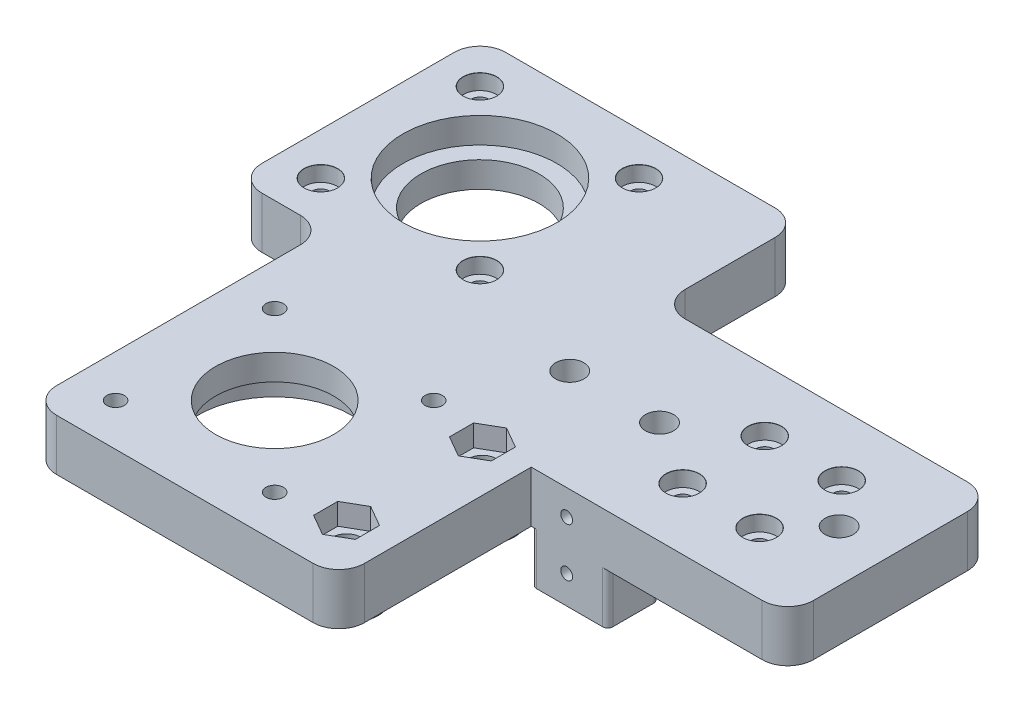
SolidWorks part; units mm, degrees
ref_plane "Front Plane" through (0, 0, 0) normal (0, 0, 1) x (1, 0, 0)
ref_plane "Top Plane" through (0, 0, 0) normal (0, 1, 0) x (1, 0, 0)
ref_plane "Right Plane" through (0, 0, 0) normal (1, 0, 0) x (0, 0, -1)
sketch "Sketch1" plane through (0, 0, 0) normal (0, 1, 0) x (1, 0, 0)
  line L0 (0, 0) -> (110, 0) construction
  line L1 (110, 0) -> (110, 20) construction
  line L2 (110, 20) -> (0, 20) construction
  line L3 (0, 20) -> (0, 0) construction
  line L4 (110, 30) -> (110, -10) construction
  line L5 (110, 30) -> (80, 30) construction
  line L6 (80, 30) -> (80, -10) construction
  line L7 (80, -10) -> (110, -10) construction
  line L8 (0, 67.5) -> (0, -47.5)
  line L16 (0, 67.5) -> (60, 67.5)
  line L18 (0, -47.5) -> (60, -47.5)
  line L19 (60, 67.5) -> (60, 30)
  line L22 (110, -10) -> (60, -10)
  line L23 (60, -10) -> (60, -47.5)
  line L24 (60, 30) -> (110, 30)
  line L25 (110, 30) -> (110, -10)
  point P8 (110, 10)
  point P13 (0, 10)
  dimension "D1" = 20
  dimension "D2" = 37.5
  dimension "D3" = 30
  dimension "D4" = 40
  dimension "D5" = 110
  dimension "D6" = 20
extrude "Boss-Extrude1" add sketch "Sketch1" along normal blind 10
fillet "Fillet1" radius 5 7 edges at (60, 5, -30) (110, 5, -30) (110, 5, 10) (0, 5, 47.5) (0, 5, -67.5) (60, 5, -67.5) (60, 5, 47.5)
sketch "Sketch3" plane through (0, 10, 0) normal (0, 1, 0) x (1, 0, 0)
  line L0 (5, -47.5) -> (55, -47.5) construction
  line L1 (0, 62.5) -> (0, -42.5) construction
  circle A0 centre (23.75, -23.75) radius 11.5
  dimension "D3" = 23
  dimension "D1" = 23.75
  dimension "D2" = 23.75
extrude "Cut-Extrude1" cut sketch "Sketch3" against normal blind 10
sketch "Sketch4" plane through (0, 0, 0) normal (0, -1, 0) x (1, 0, 0)
  line L1 (39.25, 39.25) -> (8.25, 39.25)
  line L2 (39.25, 39.25) -> (39.25, 8.25)
  line L3 (39.25, 8.25) -> (8.25, 8.25)
  line L4 (8.25, 39.25) -> (8.25, 8.25)
  line L5 (39.25, 39.25) -> (8.25, 8.25) construction
  line L6 (39.25, 8.25) -> (8.25, 39.25) construction
  point P0 (23.75, 23.75)
  dimension "D1" = 31
hole_wizard "CBORE for M3 SHCS1" positions "Sketch5" profile "Sketch6" counterbore size "M3" standard "ANSI Metric" end condition through all
sketch "Sketch5" plane through (0, 0, 0) normal (0, -1, 0) x (-1, 0, 0)
  point P0 (-39.25, -8.25)
  point P3 (-8.25, -39.25)
  point P6 (-8.25, -8.25)
  point P9 (-39.25, -39.25)
sketch "Sketch6" plane through (39.25, 0, 8.25) normal (1, 0, 0) x (0, 0, -1)
  line L0 (0, 0) -> (0, 10)
  line L1 (0, 10) -> (1.7, 10)
  line L3 (1.7, 10) -> (1.7, 3)
  line L4 (3.25, 3) -> (1.7, 3)
  line L5 (3.25, 3) -> (3.25, 0.025)
  line L6 (3.25, 0.025) -> (3.275, 0)
  line L7 (3.275, 0) -> (0, 0)
  line L8 (-3.25, 0.025) -> (-3.275, 0) construction
  line L11 (0, -6.35) -> (0, 107.95) construction
  dimension "Thru Hole Dia." = 3.4
  dimension "Thru Hole Depth" = 10
  dimension "C'Bore Dia." = 6.5
  dimension "C'Bore Depth" = 3
  dimension "Near C'Sink Dia." = 6.55
  dimension "Near C'Sink Angle" = 90
sketch "Sketch7" plane through (0, 10, 0) normal (0, 1, 0) x (1, 0, 0)
  line L1 (92.5, 18) -> (77.5, 18)
  line L2 (92.5, 18) -> (92.5, 2)
  line L3 (92.5, 2) -> (77.5, 2)
  line L4 (77.5, 18) -> (77.5, 2)
  line L5 (92.5, 18) -> (77.5, 2) construction
  line L6 (92.5, 2) -> (77.5, 18) construction
  line L7 (110, 10) -> (0, 10)
  line L8 (0, 67.5) -> (0, -47.5) construction
  line L10 (110, 30) -> (110, -10) construction
  point P0 (85, 10)
  dimension "D1" = 15
  dimension "D2" = 16
  dimension "D3" = 25
hole_wizard "CBORE for M3 SHCS2" positions "Sketch8" profile "Sketch9" counterbore size "M3" standard "ANSI Metric" end condition through all
sketch "Sketch8" plane through (0, 10, 0) normal (0, 1, 0) x (1, 0, 0)
  point P0 (77.5, 18)
  point P3 (92.5, 18)
  point P6 (92.5, 2)
  point P9 (77.5, 2)
sketch "Sketch9" plane through (77.5, 10, -18) normal (1, 0, 0) x (0, 0, 1)
  line L0 (0, 0) -> (0, 10)
  line L1 (0, 10) -> (1.7, 10)
  line L3 (1.7, 10) -> (1.7, 3)
  line L4 (3.25, 3) -> (1.7, 3)
  line L5 (3.25, 3) -> (3.25, 0.025)
  line L6 (3.25, 0.025) -> (3.275, 0)
  line L7 (3.275, 0) -> (0, 0)
  line L8 (-3.25, 0.025) -> (-3.275, 0) construction
  line L11 (0, -6.35) -> (0, 107.95) construction
  dimension "Thru Hole Dia." = 3.4
  dimension "Thru Hole Depth" = 10
  dimension "C'Bore Dia." = 6.5
  dimension "C'Bore Depth" = 3
  dimension "Near C'Sink Dia." = 6.55
  dimension "Near C'Sink Angle" = 90
sketch "Sketch10" plane through (0, 0, 0) normal (0, -1, 0) x (1, 0, 0)
  line L0 (110, -10) -> (0, -10) construction
  line L1 (110, 5) -> (110, -25) construction
  line L2 (0, -62.5) -> (0, 42.5) construction
  point P6 (100, -10)
  point P7 (30, -10)
  point P8 (47.5, -10)
  point P9 (65, -10)
  dimension "D1" = 30
  dimension "D2" = 17.5
  dimension "D3" = 17.5
  dimension "D4" = 10
hole_wizard "CBORE for M5 SHCS1" positions "Sketch13" profile "Sketch12" counterbore size "M5" standard "ANSI Metric" end condition through all
sketch "Sketch13" plane through (0, 0, 0) normal (0, -1, 0) x (-1, 0, 0)
  point P0 (-100, 10)
  point P3 (-65, 10)
  point P6 (-47.5, 10)
  point P13 (0, 0)
sketch "Sketch12" plane through (100, 0, -10) normal (1, 0, 0) x (0, 0, -1)
  line L0 (0, 0) -> (0, 10)
  line L1 (0, 10) -> (2.75, 10)
  line L3 (2.75, 10) -> (2.75, 5)
  line L4 (5, 5) -> (2.75, 5)
  line L5 (5, 5) -> (5, 0.025)
  line L6 (5, 0.025) -> (5.025, 0)
  line L7 (5.025, 0) -> (0, 0)
  line L8 (-5, 0.025) -> (-5.025, 0) construction
  line L11 (0, -6.35) -> (0, 107.95) construction
  dimension "Thru Hole Dia." = 5.5
  dimension "Thru Hole Depth" = 10
  dimension "C'Bore Dia." = 10
  dimension "C'Bore Depth" = 5
  dimension "Near C'Sink Dia." = 10.05
  dimension "Near C'Sink Angle" = 90
sketch "Sketch14" plane through (0, 10, 0) normal (0, 1, 0) x (1, 0, 0)
  line L0 (0, 10) -> (-17.5, 10)
  line L1 (0, 62.5) -> (0, -42.5) construction
  line L2 (-17.5, 10) -> (-17.5, 67.5)
  line L3 (-17.5, 67.5) -> (5, 67.5)
  line L4 (0, 62.5) -> (0, 10)
  arc A0 (5, 67.5) -> (0, 62.5) centre (5, 62.5) ccw construction
  arc A1 (5, 67.5) -> (0, 62.5) centre (5, 62.5) ccw
  dimension "D1" = 17.5
extrude "Boss-Extrude2" add sketch "Sketch14" against normal blind 10
sketch "Sketch15" plane through (0, 10, 0) normal (0, 1, 0) x (1, 0, 0)
  line L0 (-17.5, 67.5) -> (55, 67.5)
  line L1 (-17.5, 67.5) -> (-17.5, 57.5)
  line L2 (-17.5, 67.5) -> (-17.5, 10) construction
  line L3 (-17.5, 57.5) -> (60, 57.5)
  line L5 (60, 35) -> (60, 62.5) construction
  line L6 (60, 57.5) -> (60, 62.5)
  arc A2 (60, 62.5) -> (55, 67.5) centre (55, 62.5) ccw construction
  arc A3 (60, 62.5) -> (55, 67.5) centre (55, 62.5) ccw
  dimension "D1" = 10
extrude "Cut-Extrude2" cut sketch "Sketch15" against normal blind 10
fillet "Fillet2" radius 5 4 edges at (0, 5, -10) (60, 5, -57.5) (-17.5, 5, -57.5) (-17.5, 5, -10)
sketch "Sketch16" plane through (0, 10, 0) normal (0, 1, 0) x (1, 0, 0)
  line L0 (-12.5, 57.5) -> (55, 57.5) construction
  line L1 (-17.5, 52.5) -> (-17.5, 15) construction
  circle A0 centre (6.25, 33.75) radius 11.5
  dimension "D1" = 23
  dimension "D2" = 23.75
  dimension "D3" = 23.75
extrude "Cut-Extrude3" cut sketch "Sketch16" against normal through all
sketch "Sketch17" plane through (0, 10, 0) normal (0, 1, 0) x (1, 0, 0)
  line L1 (21.75, 49.25) -> (-9.25, 49.25)
  line L2 (21.75, 49.25) -> (21.75, 18.25)
  line L3 (21.75, 18.25) -> (-9.25, 18.25)
  line L4 (-9.25, 49.25) -> (-9.25, 18.25)
  line L5 (21.75, 49.25) -> (-9.25, 18.25) construction
  line L6 (21.75, 18.25) -> (-9.25, 49.25) construction
  point P0 (6.25, 33.75)
  dimension "D1" = 31
hole_wizard "CBORE for M3 SHCS3" positions "Sketch18" profile "Sketch19" counterbore size "M3" standard "ANSI Metric" end condition through all
sketch "Sketch18" plane through (0, 10, 0) normal (0, 1, 0) x (1, 0, 0)
  point P0 (-9.25, 49.25)
  point P3 (21.75, 49.25)
  point P6 (21.75, 18.25)
  point P9 (-9.25, 18.25)
sketch "Sketch19" plane through (-9.25, 10, -49.25) normal (1, 0, 0) x (0, 0, 1)
  line L0 (0, 0) -> (0, 10)
  line L1 (0, 10) -> (1.7, 10)
  line L3 (1.7, 10) -> (1.7, 3)
  line L4 (3.25, 3) -> (1.7, 3)
  line L5 (3.25, 3) -> (3.25, 0.025)
  line L6 (3.25, 0.025) -> (3.275, 0)
  line L7 (3.275, 0) -> (0, 0)
  line L8 (-3.25, 0.025) -> (-3.275, 0) construction
  line L11 (0, -6.35) -> (0, 107.95) construction
  dimension "Thru Hole Dia." = 3.4
  dimension "Thru Hole Depth" = 10
  dimension "C'Bore Dia." = 6.5
  dimension "C'Bore Depth" = 3
  dimension "Near C'Sink Dia." = 6.55
  dimension "Near C'Sink Angle" = 90
sketch "Sketch20" plane through (0, 10, 0) normal (0, 1, 0) x (1, 0, 0)
  line L0 (23.75, -23.75) -> (60, -23.75) construction
  line L1 (60, -42.5) -> (60, -10) construction
  line L2 (51, -10.51) -> (51, -36.99) construction
  line L4 (55.0703, -8.16) -> (51, -5.81)
  line L5 (51, -5.81) -> (46.9297, -8.16)
  line L6 (46.9297, -8.16) -> (46.9297, -12.86)
  line L7 (46.9297, -12.86) -> (51, -15.21)
  line L8 (51, -15.21) -> (55.0703, -12.86)
  line L9 (55.0703, -12.86) -> (55.0703, -8.16)
  line L10 (51, -32.29) -> (46.9297, -34.64)
  line L11 (46.9297, -34.64) -> (46.9297, -39.34)
  line L12 (46.9297, -39.34) -> (51, -41.69)
  line L13 (51, -41.69) -> (55.0703, -39.34)
  line L14 (55.0703, -39.34) -> (55.0703, -34.64)
  line L15 (55.0703, -34.64) -> (51, -32.29)
  line L18 (0, 5) -> (0, -42.5) construction
  circle A0 centre (51, -10.51) radius 4.0703 construction
  circle A1 centre (51, -36.99) radius 4.0703 construction
  point P8 (51, -23.75)
  point P25 (51, -36.99)
  point P26 (51, -10.51)
  dimension "D1" = 26.48
  dimension "D2" = 9
  dimension "D3" = 4.7
extrude "Cut-Extrude4" cut sketch "Sketch20" against normal blind 4.2
hole_wizard "M5 Clearance Hole1" positions "Sketch22" profile "Sketch23" hole size "M5" standard "ANSI Metric" end condition through all
sketch "Sketch22" plane through (0, 10, 0) normal (0, 1, 0) x (1, 0, 0)
  point P0 (51, -10.51)
  point P3 (51, -36.99)
sketch "Sketch23" plane through (51, 10, 10.51) normal (1, 0, 0) x (0, 0, 1)
  line L0 (0, 0) -> (0, 10)
  line L1 (0, 10) -> (2.75, 10)
  line L2 (2.75, 10) -> (2.75, 0.025)
  line L3 (2.75, 0.025) -> (2.775, 0)
  line L5 (2.775, 0) -> (0, 0)
  line L6 (-2.75, 0.025) -> (-2.775, 0) construction
  line L11 (0, -6.35) -> (0, 107.95) construction
  dimension "Thru Hole Dia." = 5.5
  dimension "Thru Hole Depth" = 10
  dimension "Near C'Sink Dia." = 5.55
  dimension "Near C'Sink Angle" = 90
sketch "Sketch24" plane through (0, 10, 0) normal (0, 1, 0) x (1, 0, 0)
  circle A0 centre (6.25, 33.75) radius 15
  dimension "D1" = 30
extrude "Cut-Extrude5" cut sketch "Sketch24" against normal blind 5
sketch "Sketch25" plane through (0, 0, 0) normal (0, -1, 0) x (1, 0, 0)
  circle A0 centre (23.75, 23.75) radius 15
  dimension "D1" = 30
extrude "Cut-Extrude6" cut sketch "Sketch25" against normal blind 5
sketch "Sketch26" plane through (0, 0, 0) normal (0, -1, 0) x (1, 0, 0)
  circle A0 centre (51, 36.99) radius 6.25
  circle A1 centre (51, 36.99) radius 2.75 construction
  circle A2 centre (51, 36.99) radius 2.75
  circle A3 centre (51, 10.51) radius 6.25
  circle A4 centre (51, 10.51) radius 2.75 construction
  circle A5 centre (51, 10.51) radius 2.75
  dimension "D1" = 12.5
extrude "Boss-Extrude3" add sketch "Sketch26" along normal blind 2.9
sketch "Sketch27" plane through (0, 10, 0) normal (0, 1, 0) x (1, 0, 0)
  line L0 (65, 30) -> (45, 30)
  line L1 (45, 30) -> (45, 57.5)
  line L2 (-12.5, 57.5) -> (55, 57.5) construction
  line L3 (45, 57.5) -> (55, 57.5)
  line L4 (60, 35) -> (60, 52.5) construction
  line L5 (60, 35) -> (60, 52.5)
  arc A0 (60, 35) -> (65, 30) centre (65, 35) ccw construction
  arc A1 (60, 52.5) -> (55, 57.5) centre (55, 52.5) ccw construction
  arc A2 (60, 35) -> (65, 30) centre (65, 35) ccw
  arc A3 (60, 52.5) -> (55, 57.5) centre (55, 52.5) ccw
  dimension "D1" = 15
extrude "Cut-Extrude7" cut sketch "Sketch27" against normal blind 10
fillet "Fillet3" radius 5 2 edges at (45, 5, -57.5) (45, 5, -30)
sketch "Sketch28" plane through (0, 0, 0) normal (0, -1, 0) x (1, 0, 0)
  line L1 (60, 10) -> (74.9, 10)
  line L2 (60, 10) -> (60, 0)
  line L3 (60, 0) -> (74.9, 0)
  line L4 (74.9, 10) -> (74.9, 0)
  dimension "D1" = 14.9
  dimension "D2" = 10
extrude "Boss-Extrude4" add sketch "Sketch28" along normal blind 10
sketch "Sketch29" plane through (0, 0, 10) normal (0, 0, 1) x (1, 0, 0)
  line L0 (66.9, 5) -> (66.9, -4.5) construction
  line L1 (74.9, -10) -> (60, -10) construction
  line L2 (60, 10) -> (105, 10) construction
  line L3 (74.9, -10) -> (74.9, 0) construction
  circle A0 centre (66.9, 5) radius 1.15
  circle A1 centre (66.9, -4.5) radius 1.15
  point P8 (66.9, 0.25)
  dimension "D1" = 2.3
  dimension "D2" = 5.5
  dimension "D3" = 5
  dimension "D4" = 8
extrude "Cut-Extrude8" cut sketch "Sketch29" against normal blind 5
fillet "Fillet4" radius 1 4 edges at (60, -5, 0) (74.9, -5, 0) (74.9, -5, 10) (60, -5, 10)
